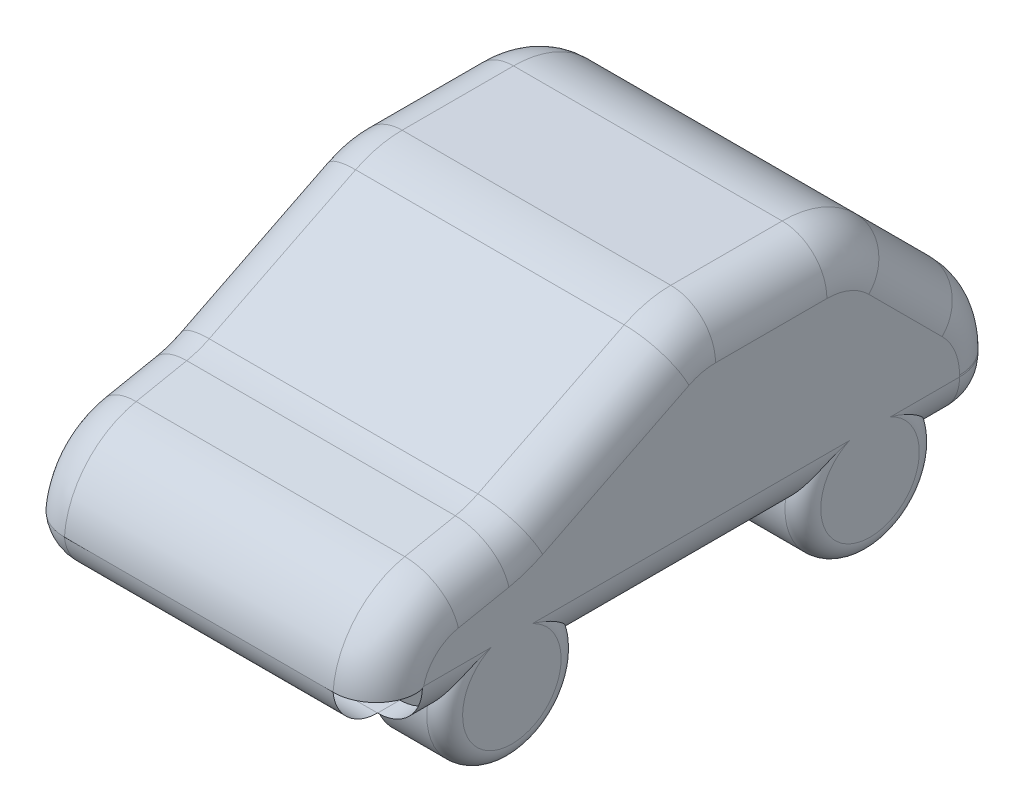
SolidWorks part; units mm, degrees
ref_plane "Ön Düzlem" through (0, 0, 0) normal (0, 0, 1) x (1, 0, 0)
ref_plane "Üst Düzlem" through (0, 0, 0) normal (0, 1, 0) x (1, 0, 0)
ref_plane "Sağ Düzlem" through (0, 0, 0) normal (1, 0, 0) x (0, 0, -1)
sketch "Çizim1" plane through (0, 0, 0) normal (1, 0, 0) x (0, 0, -1)
  line L0 (0, 5) -> (0, 3.802)
  line L1 (8.0388, 13.6078) -> (13.6868, 14.7374)
  line L2 (16.1978, 15.5989) -> (32.546, 23.773)
  line L3 (37.7436, 25) -> (50.1859, 25)
  line L4 (58.4041, 21.5959) -> (66.5959, 13.4041)
  line L5 (70, 5.1859) -> (70, 5)
  line L6 (65, 0) -> (5, 0)
  arc A0 (0, 3.802) -> (8.0388, 13.6078) centre (10, 3.802) cw
  arc A1 (13.6868, 14.7374) -> (16.1978, 15.5989) centre (11.7257, 24.5432) ccw
  arc A2 (66.5959, 13.4041) -> (70, 5.1859) centre (58.3777, 5.1859) cw
  arc A3 (50.1859, 25) -> (58.4041, 21.5959) centre (50.1859, 13.3777) cw
  arc A4 (32.546, 23.773) -> (37.7436, 25) centre (37.7436, 13.3777) cw
  arc A5 (70, 5) -> (65, 0) centre (65, 5) cw
  arc A6 (0, 5) -> (5, 0) centre (5, 5) ccw
  point P10 (0, 12)
  point P13 (15, 15)
  point P16 (70, 10)
  point P19 (55, 25)
  point P22 (35, 25)
  point P25 (70, 0)
  point P28 (0, 0)
  dimension "D9" = 10
  dimension "D10" = 10
  dimension "D11" = 11.6223
  dimension "D12" = 5
  dimension "D1" = 12
  dimension "D2" = 70
  dimension "D3" = 10
  dimension "D4" = 3
  dimension "D5" = 20
  dimension "D6" = 15
  dimension "D7" = 20
  dimension "D8" = 15
extrude "Yükseklik-Ekstrüzyon1" add sketch "Çizim1" along normal blind 40 contours A0 A6 L6 A5 L5 A2 L4 A3 L3 A4 L2 A1 L1 region at (0, 10.3988, -37.2792)
fillet "Radyus2" radius 5 22 edges at (0, 0, -35) (0, 1.4645, -68.5355) (0, 5.0929, -70) (0, 9.6335, -69.1153) (0, 17.5, -62.5) (0, 24.1153, -54.6335) (0, 25, -43.9648) (0, 24.6891, -35.0734) (0, 19.686, -24.3719) (0, 15.0844, -14.971) (0, 14.1726, -10.8628) (40, 14.1726, -10.8628) (40, 15.0844, -14.971) (40, 19.686, -24.3719) (40, 24.6891, -35.0734) (40, 25, -43.9648) (40, 24.1153, -54.6335) (40, 17.5, -62.5) (40, 9.6335, -69.1153) (40, 5.0929, -70) (40, 1.4645, -68.5355) (40, 0, -35)
sketch "Çizim2" plane through (40, 0, 0) normal (1, 0, 0) x (0, 0, -1)
  line L0 (65, 0) -> (5, 0) construction
  circle A0 centre (15, 0) radius 7.5
  circle A1 centre (55, 0) radius 7.5
  dimension "D1" = 15
  dimension "D2" = 15
  dimension "D3" = 15
extrude "Yükseklik-Ekstrüzyon2" add sketch "Çizim2" against normal blind 8
extrude "Yükseklik-Ekstrüzyon3" add sketch "Çizim2<2>" along normal blind 8 from offset 40 offset against normal yes
sketch "Çizim2<2>" plane through (40, 0, 0) normal (1, 0, 0) x (0, 0, -1) same geometry as "Çizim2"
fillet "Radyus6" radius 2 4 edges at (40, -7.5, -15) (40, -7.5, -55) (0, -7.5, -15) (0, -7.5, -55)
